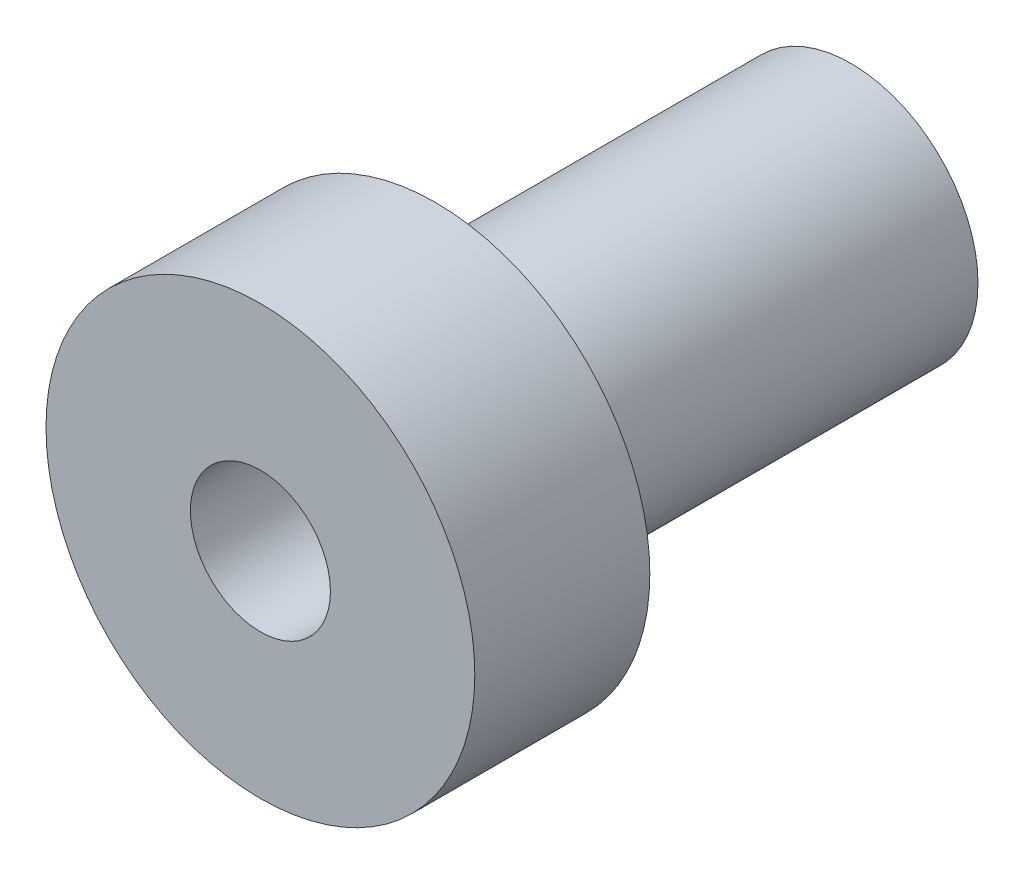
SolidWorks part; units mm, degrees
ref_plane "Płaszczyzna przednia" through (0, 0, 0) normal (0, 0, 1) x (1, 0, 0)
ref_plane "Płaszczyzna górna" through (0, 0, 0) normal (0, 1, 0) x (1, 0, 0)
ref_plane "Płaszczyzna prawa" through (0, 0, 0) normal (1, 0, 0) x (0, 0, -1)
sketch "Szkic1" plane through (0, 0, 0) normal (0, 0, 1) x (1, 0, 0)
  circle A0 centre (0, 0) radius 2.9
  dimension "D1" = 5.8
extrude "Dodanie-wyciągnięcie1" add sketch "Szkic1" along normal blind 9.5 contours A0
sketch "Szkic2" plane through (0, 0, 9.5) normal (0, 0, 1) x (1, 0, 0)
  circle A0 centre (0, 0) radius 1.6
  dimension "D1" = 3.2
extrude "Wytnij-wyciągnięcie1" cut sketch "Szkic2" against normal through all and the other way through all contours A0
sketch "Szkic3" plane through (0, 0, 9.5) normal (0, 0, 1) x (1, 0, 0)
  circle A0 centre (0, 0) radius 4.9
  dimension "D1" = 9.8
extrude "Dodanie-wyciągnięcie2" add sketch "Szkic3" along normal blind 4
sketch "Szkic4" plane through (0, 0, 0) normal (0, 0, 1) x (1, 0, 0)
  circle A0 centre (0, 0) radius 1.6
  dimension "D1" = 3.2
extrude "Wytnij-wyciągnięcie2" cut sketch "Szkic4" along normal through all
